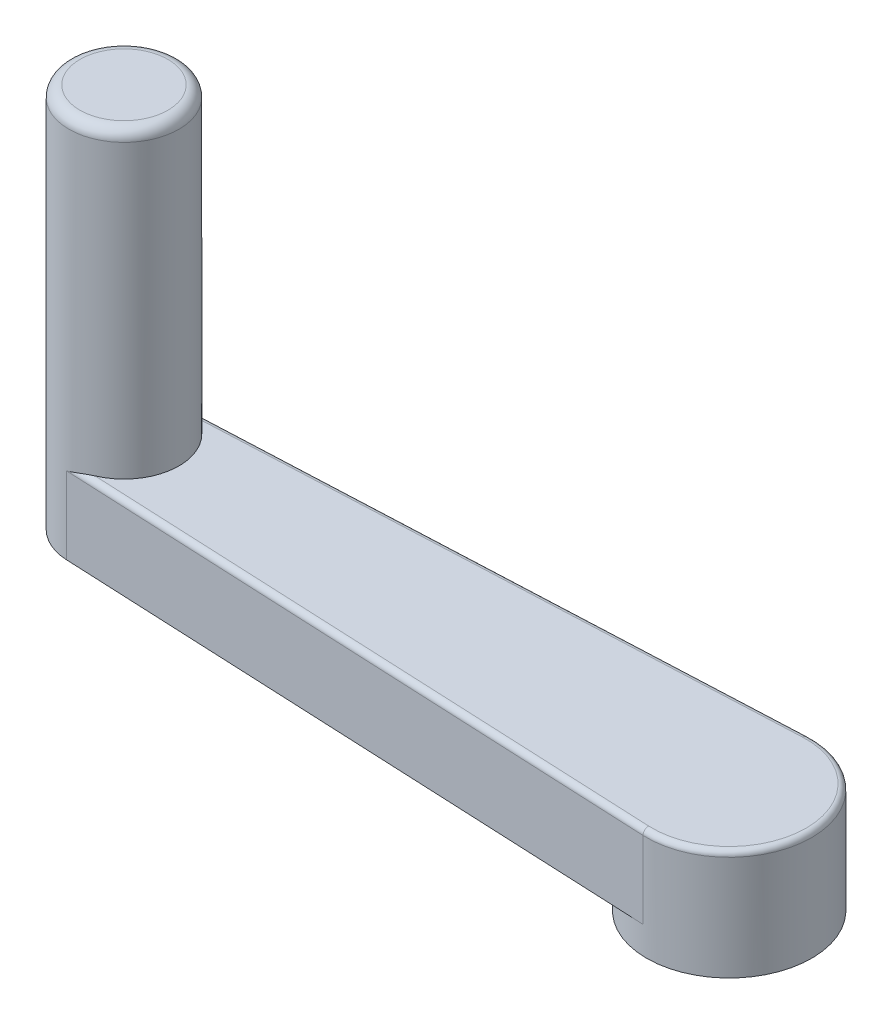
SolidWorks part; units mm, degrees
ref_plane "Front Plane" through (0, 0, 0) normal (0, 0, 1) x (1, 0, 0)
ref_plane "Top Plane" through (0, 0, 0) normal (0, 1, 0) x (1, 0, 0)
ref_plane "Right Plane" through (0, 0, 0) normal (1, 0, 0) x (0, 0, -1)
sketch "Sketch2" plane through (0, 0, 0) normal (0, 1, 0) x (1, 0, 0)
  line L0 (-55.2273, -4.9948) -> (-0.3409, -7.4922)
  line L1 (-0.3409, 7.4922) -> (-55.2273, 4.9948)
  circle A0 centre (0, 0) radius 7.5
  circle A1 centre (-55, 0) radius 5
  point P9 (0, 0)
  point P10 (-54.7585, -5.1623)
  point P11 (-55.2273, 0)
  point P12 (0, 0)
  dimension "D1" = 15
  dimension "D2" = 10
  dimension "D3" = 55
extrude "Boss-Extrude1" add sketch "Sketch2" along normal blind 7.5 contours A1 | A1 L0 A0 L1 | A0 region at (-27.3044, 0, 0) region at (-55, 0, 0) region at (0, 0, 0)
extrude "Boss-Extrude2" add sketch "Sketch2<3>" against normal blind 2.5 contours A0 region at (0, 0, 0)
sketch "Sketch2<3>" plane through (0, 0, 0) normal (0, 1, 0) x (1, 0, 0) same geometry as "Sketch2"
extrude "Boss-Extrude3" add sketch "Sketch2<4>" along normal blind 35 contours A1 region at (-55, 0, 0)
sketch "Sketch2<4>" plane through (0, 0, 0) normal (0, 1, 0) x (1, 0, 0) same geometry as "Sketch2"
sketch "Sketch3" plane through (0, -2.5, 0) normal (0, -1, 0) x (1, 0, 0)
  circle A0 centre (0, 0) radius 4
  dimension "D1" = 8
extrude "Cut-Extrude1" cut sketch "Sketch3" against normal blind 6
fillet "Fillet1" radius 1 1 edges at (-55, 35, 5)
fillet "Fillet2" radius 0.5 3 edges at (7.5, 7.5, 0) (-27.7841, 7.5, 6.2435) (-27.7841, 7.5, -6.2435)
